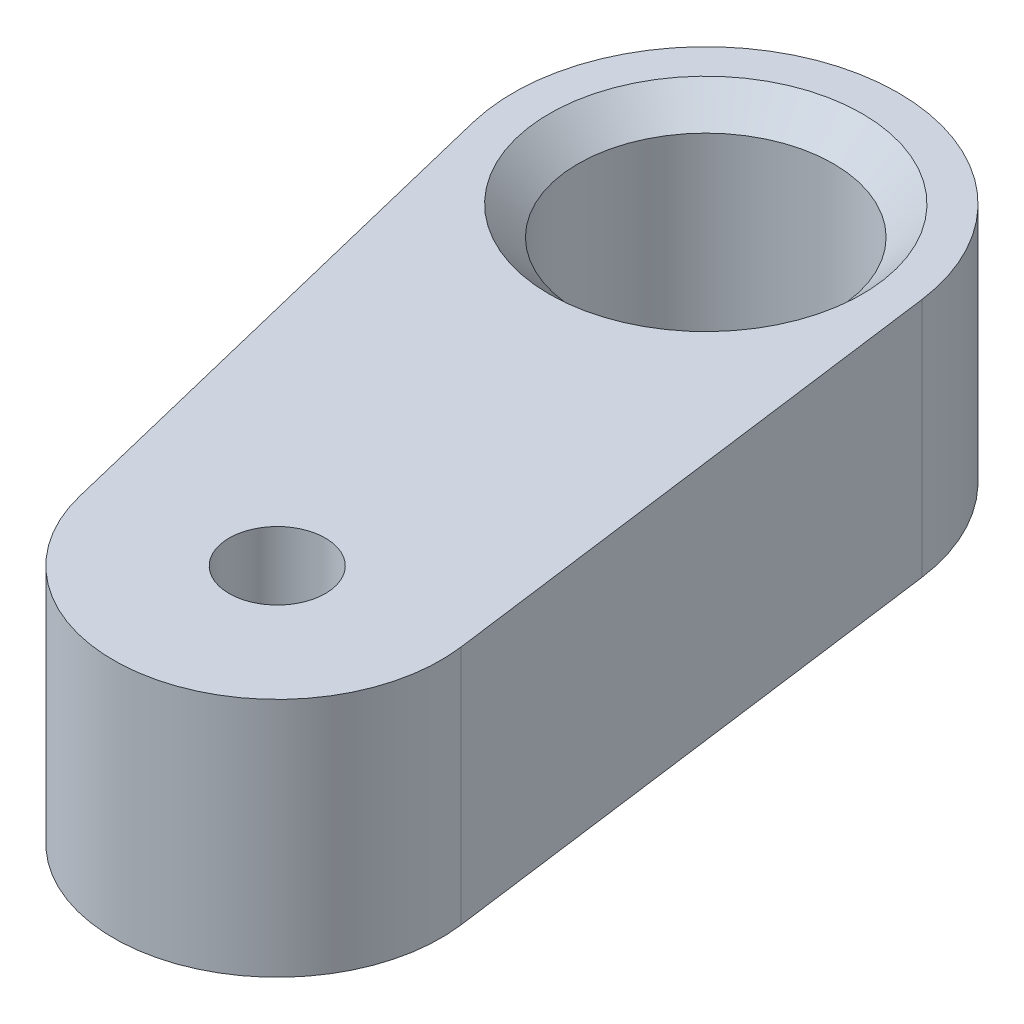
SolidWorks part; units mm, degrees
note: The reader was unsure of these and kept them because the rebuilt part matched: shared geometry of "Sketch1<3>".
ref_plane "Front Plane" through (0, 0, 0) normal (0, 0, 1) x (1, 0, 0)
ref_plane "Top Plane" through (0, 0, 0) normal (0, 1, 0) x (1, 0, 0)
ref_plane "Right Plane" through (0, 0, 0) normal (1, 0, 0) x (0, 0, -1)
ref_plane "Plane1" through (0, 33, 0) normal (0, 1, 0) x (1, 0, 0)
sketch "Sketch1" plane through (0, 33, 0) normal (0, 1, 0) x (1, 0, 0)
  line L0 (3.5261, -9.2917) -> (0.5929, -12.6347) construction
  line L1 (-3.8858, -0.9489) -> (-1.2435, -11.7698)
  line L2 (3.9653, 0.526) -> (5.43, -10.5162)
  line L8 (-32.1913, -14.8231) -> (-30.8181, -19.7137)
  line L9 (-30.8181, -19.7137) -> (0.8067, -13.7728)
  line L10 (0.8067, -13.7728) -> (0.5929, -12.6347)
  line L11 (0.5929, -12.6347) -> (4.0327, -11.9885)
  line L12 (4.0327, -11.9885) -> (3.5261, -9.2917)
  line L13 (3.5261, -9.2917) -> (0.0863, -9.9379)
  line L14 (0.0863, -9.9379) -> (-0.1275, -8.7998)
  line L15 (-0.1275, -8.7998) -> (-32.1913, -14.8231)
  line L16 (-32.1913, -14.8231) -> (-30.8181, -19.7137) construction
  line L17 (-30.8181, -19.7137) -> (0.8067, -13.7728) construction
  line L18 (0.8067, -13.7728) -> (0.5929, -12.6347) construction
  line L19 (0.5929, -12.6347) -> (4.0327, -11.9885) construction
  line L20 (4.0327, -11.9885) -> (3.5261, -9.2917) construction
  line L21 (3.5261, -9.2917) -> (0.0863, -9.9379) construction
  line L22 (0.0863, -9.9379) -> (-0.1275, -8.7998) construction
  line L23 (-0.1275, -8.7998) -> (-32.1913, -14.8231) construction
  circle A0 centre (0, 0) radius 5.125 construction
  circle A1 centre (0, 0) radius 5.125 construction
  circle A2 centre (0, 0) radius 2.65
  circle A3 centre (2.0595, -10.9632) radius 2.6
  circle A4 centre (0, 0) radius 4
  circle A5 centre (2.0595, -10.9632) radius 3.4
  circle A6 centre (2.0595, -10.9632) radius 1
  dimension "D2" = 5.2
  dimension "D3" = 5.3
  dimension "D4" = 8
  dimension "D5" = 0.8
  dimension "D6" = 2
  dimension "D1" = 0
extrude "Boss-Extrude1" add sketch "Sketch1" along normal blind 3.2 contours A4 A2 | A5 L2 A4 L1 | A5 A3
extrude "Boss-Extrude2" add sketch "Sketch1<3>" along normal blind 1.8 from surface at 3.2 contours A2 | A4 A2 | A5 L2 A4 L1 | A5 A3 | A3
sketch "Sketch1<3>" plane through (0, 33, 0) normal (0, 1, 0) x (1, 0, 0) same geometry as "Sketch1"
chamfer "Chamfer1" distance 0.6 angle 45 2 edges at (0, 33, 2.65) (0, 38, 2.65)
fillet "Fillet3" radius 0.4 1 edges at (2.0595, 33, 13.5632)
